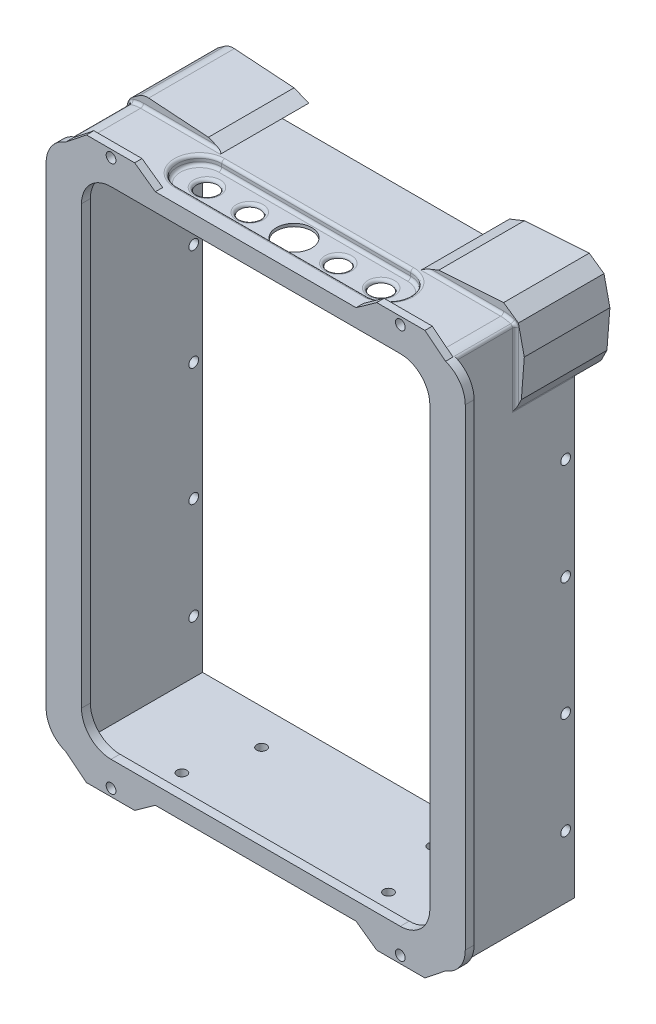
SolidWorks part; units mm, degrees
ref_plane "前视基准面" through (0, 0, 0) normal (0, 0, 1) x (1, 0, 0)
ref_plane "上视基准面" through (0, 0, 0) normal (0, 1, 0) x (1, 0, 0)
ref_plane "右视基准面" through (0, 0, 0) normal (1, 0, 0) x (0, 0, -1)
sketch "草图1" plane through (0, 0, 0) normal (0, 0, 1) x (1, 0, 0)
  line L0 (-65, -90) -> (65, -90) construction
  line L1 (65, -90) -> (65, 90) construction
  line L2 (-65, 90) -> (-65, -90) construction
  line L3 (65, 90) -> (-65, 90) construction
  line L4 (-65, -90) -> (65, -90)
  line L5 (65, -90) -> (65, 90)
  line L6 (-65, 90) -> (-65, -90)
  line L7 (65, 90) -> (-65, 90)
  line L8 (-61, 86) -> (-61, -86)
  line L9 (-61, -86) -> (61, -86)
  line L10 (61, -86) -> (61, 86)
  line L11 (61, 86) -> (-61, 86)
  dimension "D1" = 4
extrude "凸台-拉伸1" add sketch "草图1" along normal blind 40
sketch "草图3" plane through (0, 0, 0) normal (0, 0, 1) x (1, 0, 0)
  line L0 (-65, -90) -> (65, -90) construction
  line L1 (-71, 90) -> (71, 90)
  line L2 (-71, 90) -> (-71, -90)
  line L3 (-71, -90) -> (71, -90)
  line L4 (71, 90) -> (71, -90)
  line L5 (0, -90) -> (0, 90) construction
  line L6 (-71, 0) -> (71, 0) construction
  line L7 (65, -90) -> (65, 90) construction
  line L8 (61, -86) -> (61, 86) construction
  line L9 (59, 84) -> (-59, 84)
  line L10 (59, 84) -> (59, -84)
  line L11 (59, -84) -> (-59, -84)
  line L12 (-59, 84) -> (-59, -84)
  line L13 (0, -84) -> (0, 84) construction
  line L14 (59, 0) -> (-59, 0) construction
  line L15 (-61, -86) -> (61, -86) construction
  point P0 (0, 0)
  point P11 (0, 0)
  dimension "D1" = 0
  dimension "D2" = 6
  dimension "D3" = 2
  dimension "D4" = 2
extrude "凸台-拉伸2" add sketch "草图3" along normal blind 3 from offset 40
fillet "圆角1" radius 10 8 edges at (59, 84, 41.5) (71, 90, 41.5) (-71, 90, 41.5) (-59, 84, 41.5) (59, -84, 41.5) (71, -90, 41.5) (-59, -84, 41.5) (-71, -90, 41.5)
sketch "草图4" plane through (0, -90, 0) normal (0, -1, 0) x (1, 0, 0)
  line L0 (0, 0) -> (0, 71.0699) construction
  line L1 (-61, 40) -> (61, 40) construction
  circle A0 centre (-35, 33) radius 1.65
  circle A1 centre (35, 33) radius 1.65
  circle A2 centre (-29, 12) radius 1.65
  circle A3 centre (29, 12) radius 1.65
  dimension "D1" = 3.3
  dimension "D4" = 3.3
  dimension "D2" = 7
  dimension "D3" = 35
  dimension "D5" = 29
  dimension "D6" = 12
extrude "切除-拉伸1" cut sketch "草图4" against normal up to surface (4 mm away) up to face at (0, -86, 20)
sketch "草图5" plane through (0, -90, 0) normal (0, -1, 0) x (1, 0, 0)
  line L0 (-32.1734, 38.0342) -> (-37.9465, 37.965)
  line L1 (-33.0214, 36.524) -> (-37.0625, 36.4755)
  line L2 (-37.0625, 36.4755) -> (-39.0412, 32.9516)
  line L3 (-39.0412, 32.9516) -> (-36.9786, 29.476)
  line L4 (-36.9786, 29.476) -> (-32.9375, 29.5245)
  line L5 (-32.9375, 29.5245) -> (-30.9588, 33.0484)
  line L6 (-30.9588, 33.0484) -> (-33.0214, 36.524)
  line L7 (-37.9465, 37.965) -> (-40.7731, 32.9308)
  line L8 (-40.7731, 32.9308) -> (-37.8266, 27.9658)
  line L9 (-37.8266, 27.9658) -> (-32.0535, 28.035)
  line L10 (-32.0535, 28.035) -> (-29.2269, 33.0692)
  line L11 (-29.2269, 33.0692) -> (-32.1734, 38.0342)
  line L18 (0, -92.499) -> (0, 86.499) construction
  line L19 (40.7731, 32.9308) -> (37.8266, 27.9658)
  line L20 (39.0412, 32.9516) -> (36.9786, 29.476)
  line L21 (36.9786, 29.476) -> (32.9375, 29.5245)
  line L22 (37.8266, 27.9658) -> (32.0535, 28.035)
  line L23 (32.0535, 28.035) -> (29.2269, 33.0692)
  line L24 (32.9375, 29.5245) -> (30.9588, 33.0484)
  line L25 (30.9588, 33.0484) -> (33.0214, 36.524)
  line L26 (29.2269, 33.0692) -> (32.1734, 38.0342)
  line L27 (33.0214, 36.524) -> (37.0625, 36.4755)
  line L28 (32.1734, 38.0342) -> (37.9465, 37.965)
  line L29 (37.0625, 36.4755) -> (39.0412, 32.9516)
  line L30 (37.9465, 37.965) -> (40.7731, 32.9308)
  circle A0 centre (-35, 33) radius 3.5 construction
  dimension "D1" = 7
  dimension "D3" = 30.9588
  dimension "D2" = 1.5
extrude "凸台-拉伸3" add sketch "草图5" along normal blind 4
sketch "草图7" plane through (0, 90, 0) normal (0, 1, 0) x (1, 0, 0)
  line L0 (0, 0) -> (0, -59.957) construction
  line L1 (61, 0) -> (-61, 0) construction
  line L2 (32, -30) -> (-32, -30) construction
  line L3 (32, -37.5) -> (-32, -37.5)
  line L4 (32, -22.5) -> (-32, -22.5)
  arc A0 (32, -37.5) -> (32, -22.5) centre (32, -30) ccw
  arc A1 (-32, -22.5) -> (-32, -37.5) centre (-32, -30) ccw
  point P6 (0, -30)
  dimension "D1" = 64
  dimension "D2" = 15
  dimension "D3" = 30
extrude "切除-拉伸2" cut sketch "草图7" against normal blind 3
sketch "草图8" plane through (0, 90, 0) normal (0, 1, 0) x (1, 0, 0)
  line L0 (0, 0) -> (0, -63.4893) construction
  line L1 (-32, -37.5) -> (32, -37.5) construction
  line L2 (0, -30) -> (-47.3705, -30) construction
  circle A0 centre (0, -30) radius 6
  circle A1 centre (-15, -30) radius 3.5
  circle A2 centre (-29.5, -30) radius 3.5
  circle A3 centre (29.5, -30) radius 3.5
  circle A4 centre (15, -30) radius 3.5
  dimension "D1" = 12
  dimension "D3" = 7
  dimension "D2" = 7.5
  dimension "D4" = 15
  dimension "D5" = 14.5
extrude "切除-拉伸3" cut sketch "草图8" against normal up to surface (4 mm away) up to face at (0, 86, 20)
sketch "草图11" plane through (0, 0, 0) normal (0, 0, -1) x (-1, 0, 0)
  line L0 (-65, 64) -> (-67, 68)
  line L1 (-65, -89.1652) -> (-65, 89.1652) construction
  line L2 (-67, 68) -> (-68, 81)
  line L3 (-68, 81) -> (-66, 90)
  line L4 (-66, 90) -> (-61, 93.5)
  line L5 (-61, 93.5) -> (-39, 92)
  line L6 (-39, 92) -> (-34, 90)
  line L7 (-61, 90) -> (61, 90) construction
  line L8 (-61, 90) -> (-34, 90)
  line L9 (-65, 64) -> (-65, 89.1652)
  line L10 (0, 0) -> (0, 18.954) construction
  line L11 (65, 64) -> (65, 89.1652)
  line L12 (61, 90) -> (34, 90)
  line L13 (39, 92) -> (34, 90)
  line L14 (61, 93.5) -> (39, 92)
  line L15 (66, 90) -> (61, 93.5)
  line L16 (68, 81) -> (66, 90)
  line L17 (67, 68) -> (68, 81)
  line L18 (65, 64) -> (67, 68)
  arc A0 (-61, 90) -> (-65, 89.1652) centre (-61, 80) ccw construction
  arc A1 (-61, 90) -> (-65, 89.1652) centre (-61, 80) ccw
  arc A2 (61, 90) -> (65, 89.1652) centre (61, 80) cw
  line M5 (61, 90) -> (-61, 90)
  arc M6 (-61, 90) -> (-65, 89.1652) centre (-61, 80) ccw
  line M7 (-65, 89.1652) -> (-65, -89.1652)
  line M11 (65, -89.1652) -> (65, 89.1652)
  arc M12 (65, 89.1652) -> (61, 90) centre (61, 80) ccw
  dimension "D1" = 39
  dimension "D2" = 34
  dimension "D3" = 61
  dimension "D4" = 1.5
  dimension "D5" = 66
  dimension "D6" = 81
  dimension "D7" = 68
  dimension "D8" = 64
  dimension "D9" = 2
  dimension "D10" = 3
  dimension "D11" = 3.5
  dimension "D12" = 90
extrude "凸台-拉伸4" add sketch "草图11" against normal blind 20 and the other way blind 9 contours L18 L17 L16 L15 L14 L13 M11 M5 M12 | L6 L5 L4 L3 L2 L0 M7 M6 M5 region at (-36.6672, 90.5821, 0) region at (65.5974, 66.2013, 0)
fillet "圆角4" radius 1 10 edges at (-63.0431, 89.7891, 20) (63.0431, 89.7891, 20) (-65, 64, 10) (-65, 89.1652, 30) (-65, 76.5826, 20) (-47.5, 90, 20) (65, 64, 10) (65, 89.1652, 30) (65, 76.5826, 20) (47.5, 90, 20)
fillet "圆角5" radius 5 3 edges at (-68, 81, 5.5) (-66, 90, 5.5) (-61, 93.5, 5.5)
sketch "草图12" plane through (0, 0, 43) normal (0, 0, 1) x (1, 0, 0)
  line L0 (64.3333, 89.4281) -> (57.3333, 95)
  line L1 (57.3333, 95) -> (41, 95)
  line L2 (41, 95) -> (34, 90)
  line L3 (61, 90) -> (-61, 90) construction
  line L4 (34, 90) -> (61, 90)
  line L5 (0, -89.499) -> (0, 89.499) construction
  line L6 (-34, 90) -> (-61, 90)
  line L7 (-41, 95) -> (-34, 90)
  line L8 (-57.3333, 95) -> (-41, 95)
  line L9 (-64.3333, 89.4281) -> (-57.3333, 95)
  line L10 (0, 0) -> (-134.8976, 0) construction
  line L11 (34, -90) -> (61, -90)
  line L12 (41, -95) -> (34, -90)
  line L13 (57.3333, -95) -> (41, -95)
  line L14 (64.3333, -89.4281) -> (57.3333, -95)
  line L15 (-64.3333, -89.4281) -> (-57.3333, -95)
  line L16 (-57.3333, -95) -> (-41, -95)
  line L17 (-41, -95) -> (-34, -90)
  line L18 (-34, -90) -> (-61, -90)
  arc A0 (61, 90) -> (64.3333, 89.4281) centre (61, 80) cw
  arc A1 (-61, 90) -> (-64.3333, 89.4281) centre (-61, 80) ccw
  arc A2 (61, -90) -> (64.3333, -89.4281) centre (61, -80) ccw
  arc A3 (-61, -90) -> (-64.3333, -89.4281) centre (-61, -80) cw
  dimension "D1" = 5
  dimension "D2" = 7
  dimension "D3" = 7
extrude "凸台-拉伸5" add sketch "草图12" against normal blind 2.5
sketch "草图13" plane through (0, 0, 40.5) normal (0, 0, -1) x (-1, 0, 0)
  line L0 (41, 95) -> (57.3333, 95) construction
  line L1 (0, 0) -> (-7.6064, 0) construction
  line L2 (0, 0) -> (0, -14.4996) construction
  circle A0 centre (49, 92.5) radius 1.65
  circle A1 centre (-49, 92.5) radius 1.65
  circle A2 centre (-49, -92.5) radius 1.65
  circle A3 centre (49, -92.5) radius 1.65
  dimension "D1" = 3.3
  dimension "D2" = 2.5
  dimension "D3" = 8
extrude "切除-拉伸4" cut sketch "草图13" against normal blind 3
fillet "圆角6" radius 1 4 edges at (-29.5, 87, 33.5) (-15, 87, 33.5) (15, 87, 33.5) (29.5, 87, 33.5)
fillet "圆角7" radius 1 4 edges at (39.5, 87, 30) (0, 87, 37.5) (-39.5, 87, 30) (0, 87, 22.5)
fillet "圆角8" radius 1 4 edges at (0, 90, 22.5) (39.5, 90, 30) (0, 90, 37.5) (-39.5, 90, 30)
sketch "草图15" plane through (-65, 0, 0) normal (-1, 0, 0) x (0, 0, 1)
  line L0 (0, 63.7639) -> (0, -89.1652) construction
  line L1 (21, 63.7639) -> (0, 63.7639) construction
  line L2 (0, -89.1652) -> (40, -89.1652) construction
  circle A0 centre (3, -33.5) radius 1.65
  circle A1 centre (3, -68) radius 1.65
  circle A2 centre (3, 6.5) radius 1.65
  circle A3 centre (3, 41) radius 1.65
  dimension "D1" = 3.3
  dimension "D2" = 3
  dimension "D3" = 57.2639
  dimension "D4" = 22.7639
  dimension "D5" = 3
  dimension "D6" = 3
  dimension "D7" = 3
  dimension "D8" = 21.1652
  dimension "D9" = 55.6652
extrude "切除-拉伸5" cut sketch "草图15" against normal up to surface (4 mm away) contours A3 | A2 | A0 | A1 up to face at (-61, 0, 20)
mirror "镜向1" about plane through (0, 0, 0) normal (1, 0, 0) of "切除-拉伸5"
